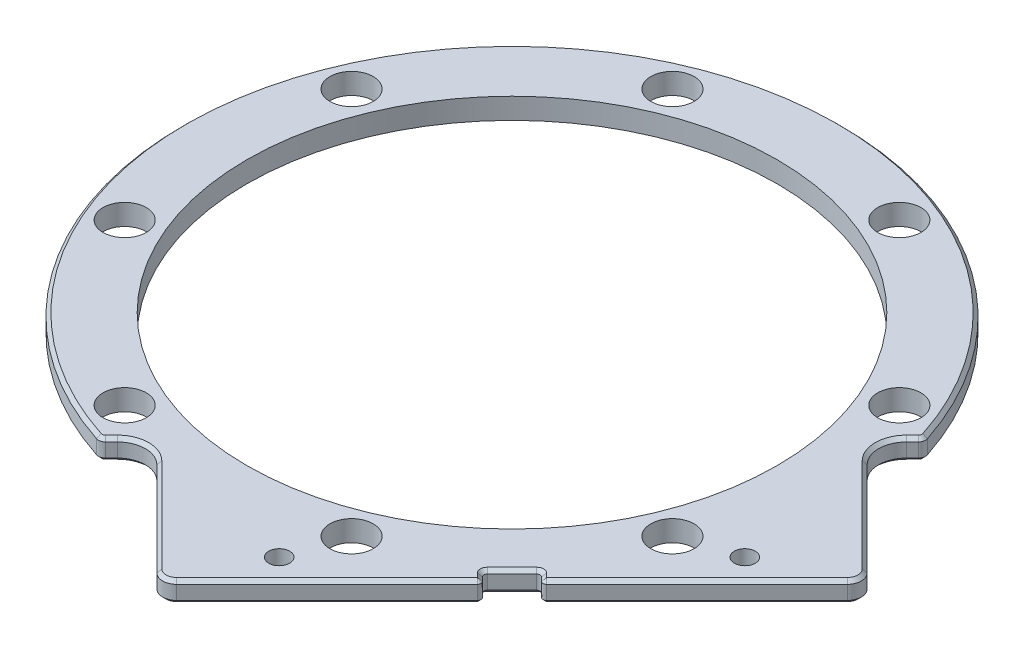
SolidWorks part; units mm, degrees
other "标注1"
sketch "草图3" plane through (-47.25, 0, -56.6457) normal (-0.9674, -0.159, -0.1974) x (-0.1681, 0.9853, 0.0301)
ref_plane "前视基准面" through (0, 0, 0) normal (0, 0, 1) x (1, 0, 0)
ref_plane "上视基准面" through (0, 0, 0) normal (0, 1, 0) x (1, 0, 0)
ref_plane "右视基准面" through (0, 0, 0) normal (1, 0, 0) x (0, 0, -1)
sketch "草图1" plane through (0, 0, 0) normal (0, 1, 0) x (1, 0, 0)
  line L1 (16.264, 39.2649) -> (-16.264, 39.2649) construction
  line L2 (-16.264, 39.2649) -> (-39.2649, 16.264) construction
  line L3 (-39.2649, 16.264) -> (-39.2649, -16.264) construction
  line L4 (-39.2649, -16.264) -> (-16.264, -39.2649) construction
  line L5 (-16.264, -39.2649) -> (16.264, -39.2649) construction
  line L6 (16.264, -39.2649) -> (39.2649, -16.264) construction
  line L7 (39.2649, -16.264) -> (39.2649, 16.264) construction
  line L8 (39.2649, 16.264) -> (16.264, 39.2649) construction
  circle A0 centre (0, 0) radius 47.25
  circle A1 centre (0, 0) radius 38
  circle A2 centre (0, 0) radius 42.5 construction
  circle A3 centre (-16.264, 39.2649) radius 3.1
  circle A4 centre (16.264, 39.2649) radius 3.1
  circle A5 centre (39.2649, 16.264) radius 3.1
  circle A6 centre (39.2649, -16.264) radius 3.1
  circle A7 centre (16.264, -39.2649) radius 3.1
  circle A8 centre (-16.264, -39.2649) radius 3.1
  circle A9 centre (-39.2649, -16.264) radius 3.1
  circle A10 centre (-39.2649, 16.264) radius 3.1
  dimension "D1" = 76
  dimension "D2" = 94.5
  dimension "D3" = 6.2
  dimension "D4" = 85
extrude "凸台-拉伸1" add sketch "草图1" along normal blind 3
sketch "草图4" plane through (0, 3, 0) normal (0, 1, 0) x (1, 0, 0)
  line L0 (43.8406, 12.7279) -> (44.7197, 13.607) construction
  line L1 (57.2756, -6.364) -> (43.8406, 7.0711) construction
  line L2 (-13.607, -44.7197) -> (-12.7279, -43.8406) construction
  line L3 (9.1924, -57.2756) -> (57.2756, -9.1924) construction
  line L4 (-7.0711, -43.8406) -> (6.364, -57.2756) construction
  line L5 (43.8406, 12.7279) -> (44.7197, 13.607)
  line L6 (57.2756, -6.364) -> (43.8406, 7.0711)
  line L7 (-13.607, -44.7197) -> (-12.7279, -43.8406)
  line L8 (9.1924, -57.2756) -> (57.2756, -9.1924)
  line L9 (-7.0711, -43.8406) -> (6.364, -57.2756)
  line L10 (-17.8963, -45.6149) -> (6.0019, -69.183)
  line L11 (6.0019, -69.183) -> (84.3795, 11.8292)
  line L12 (84.3795, 11.8292) -> (45.6149, 17.8963)
  arc A0 (44.7197, 13.607) -> (45.6149, 17.8963) centre (41.8913, 16.4354) ccw construction
  arc A1 (43.8406, 12.7279) -> (43.8406, 7.0711) centre (46.669, 9.8995) ccw construction
  arc A2 (57.2756, -9.1924) -> (57.2756, -6.364) centre (55.8614, -7.7782) ccw construction
  arc A3 (-17.8963, -45.6149) -> (-13.607, -44.7197) centre (-16.4354, -41.8913) ccw construction
  arc A4 (-7.0711, -43.8406) -> (-12.7279, -43.8406) centre (-9.8995, -46.669) ccw construction
  arc A5 (6.364, -57.2756) -> (9.1924, -57.2756) centre (7.7782, -55.8614) ccw construction
  arc A6 (44.7197, 13.607) -> (45.6149, 17.8963) centre (41.8913, 16.4354) ccw
  arc A7 (43.8406, 12.7279) -> (43.8406, 7.0711) centre (46.669, 9.8995) ccw
  arc A8 (57.2756, -9.1924) -> (57.2756, -6.364) centre (55.8614, -7.7782) ccw
  arc A9 (-17.8963, -45.6149) -> (-13.607, -44.7197) centre (-16.4354, -41.8913) ccw
  arc A10 (-7.0711, -43.8406) -> (-12.7279, -43.8406) centre (-9.8995, -46.669) ccw
  arc A11 (6.364, -57.2756) -> (9.1924, -57.2756) centre (7.7782, -55.8614) ccw
extrude "切除-拉伸1" cut sketch "草图4" against normal through all both and the other way through all
sketch "草图5" plane through (0, 0, 0) normal (0, -1, 0) x (1, 0, 0)
  line L0 (57.2756, 6.364) -> (43.8406, -7.0711) construction
  line L1 (9.1924, 57.2756) -> (57.2756, 9.1924) construction
  line L2 (-7.0711, 43.8406) -> (6.364, 57.2756) construction
  line L3 (57.2756, 6.364) -> (43.8406, -7.0711)
  line L4 (9.1924, 57.2756) -> (57.2756, 9.1924)
  line L5 (-7.0711, 43.8406) -> (6.364, 57.2756)
  arc A0 (57.2756, 6.364) -> (57.2756, 9.1924) centre (55.8614, 7.7782) ccw construction
  arc A1 (9.1924, 57.2756) -> (6.364, 57.2756) centre (7.7782, 55.8614) ccw construction
  arc A2 (57.2756, 6.364) -> (57.2756, 9.1924) centre (55.8614, 7.7782) ccw
  arc A3 (9.1924, 57.2756) -> (6.364, 57.2756) centre (7.7782, 55.8614) ccw
  arc A4 (-7.0711, 43.8406) -> (43.8406, -7.0711) centre (3.5678, 3.5678) cw
extrude "凸台-拉伸2" add sketch "草图5" against normal up to surface (3 mm away) up to face at (16.1629, 3, 16.1629)
fillet "圆角1" radius 1 2 edges at (45.1096, 1.5, -14.0601) (-14.0601, 1.5, 45.1096)
sketch "草图6" plane through (0, 0, 0) normal (0, -1, 0) x (1, 0, 0)
  line L0 (29.8399, 34.0825) -> (34.0825, 29.8399)
  line L1 (57.2756, 9.1924) -> (9.1924, 57.2756) construction
  line L2 (9.1924, 57.2756) -> (57.2756, 9.1924) construction
  line L3 (33.234, 33.234) -> (31.9612, 31.9612) construction
  line L4 (31.2541, 35.2139) -> (35.2139, 31.2541) construction
  line L5 (34.0825, 29.8399) -> (35.3553, 31.1127)
  line L6 (35.3553, 31.1127) -> (31.1127, 35.3553)
  line L7 (31.1127, 35.3553) -> (29.8399, 34.0825)
  point P4 (33.234, 33.234)
  point P9 (31.9612, 31.9612)
  dimension "D1" = 6
  dimension "D2" = 1.8
extrude "切除-拉伸2" cut sketch "草图6" against normal through all both and the other way through all
fillet "圆角2" radius 0.5 4 edges at (35.3553, 1.5, 31.1127) (34.0825, 1.5, 29.8399) (29.8399, 1.5, 34.0825) (31.1127, 1.5, 35.3553)
chamfer "倒角1" distance 0.5 angle 45 38 edges at (-13.1549, 0, 44.2676) (-14.0554, 0, 44.9597) (-9.8995, 0, 42.669) (-33.4108, 0, -33.4108) (-0.3536, 0, 50.5581) (44.9597, 0, -14.0554) (7.7782, 0, 57.8614) (44.2676, 0, -13.1549) (42.669, 0, -9.8995) (57.8614, 0, 7.7782) (50.5581, 0, -0.3536) (-14.0554, 3, 44.9597) (-33.4108, 3, -33.4108) (-13.1549, 3, 44.2676) (44.9597, 3, -14.0554) (-9.8995, 3, 42.669) (44.2676, 3, -13.1549) (-0.3536, 3, 50.5581) (42.669, 3, -9.8995) (7.7782, 3, 57.8614) (50.5581, 3, -0.3536) (57.8614, 3, 7.7782) (19.9758, 0, 46.4923) (30.9056, 0, 35.3553) (30.4763, 0, 34.7189) (30.047, 0, 34.0825) (31.9612, 0, 31.9612) (34.0825, 0, 30.047) (34.7189, 0, 30.4763) (35.3553, 0, 30.9056) (19.9758, 3, 46.4923) (30.9056, 3, 35.3553) (30.4763, 3, 34.7189) (30.047, 3, 34.0825) (31.9612, 3, 31.9612) (34.0825, 3, 30.047) (34.7189, 3, 30.4763) (35.3553, 3, 30.9056)
sketch "草图7" plane through (0, 0, 0) normal (0, -1, 0) x (1, 0, 0)
  circle A1 centre (13.6786, 47.0539) radius 1.5 construction
  circle A2 centre (13.6786, 47.0539) radius 1.5
extrude "切除-拉伸3" cut sketch "草图7" against normal through all both and the other way through all
sketch "草图8" plane through (0, 0, 0) normal (0, -1, 0) x (1, 0, 0)
  circle A0 centre (47.0539, 13.6786) radius 1.5 construction
  circle A1 centre (47.0539, 13.6786) radius 1.5
extrude "切除-拉伸4" cut sketch "草图8" against normal through all both and the other way through all
